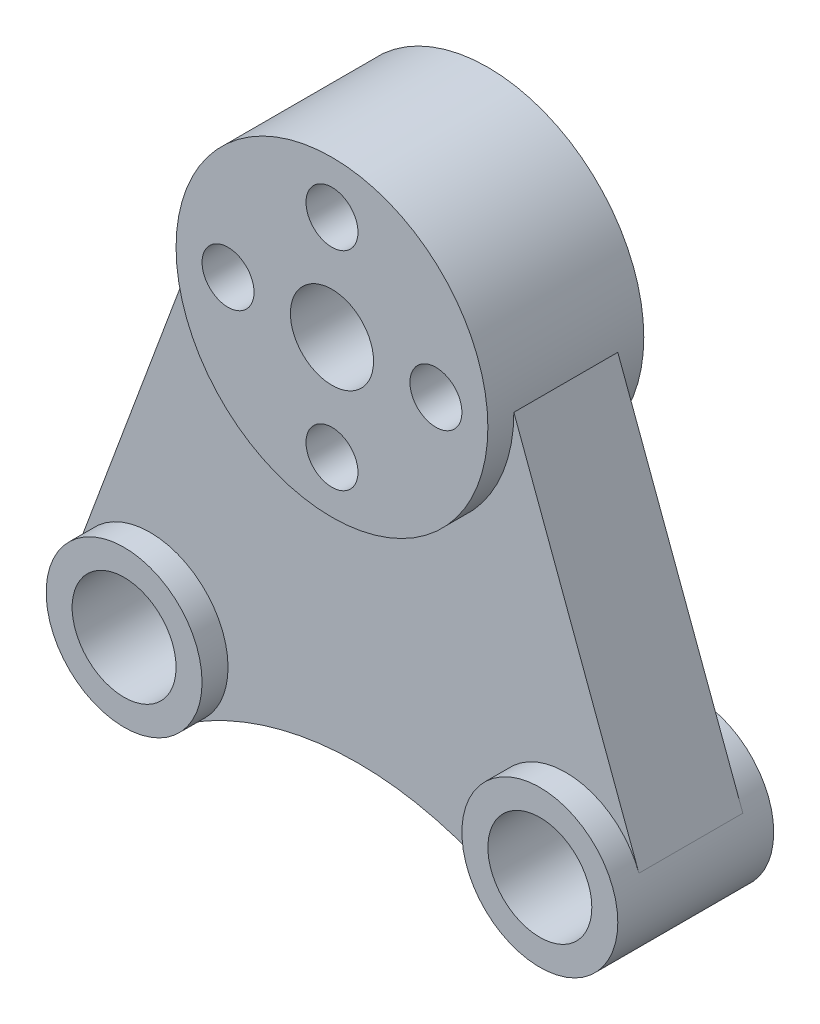
SolidWorks part; units mm, degrees
ref_plane "Front Plane" through (0, 0, 0) normal (0, 0, 1) x (1, 0, 0)
ref_plane "Top Plane" through (0, 0, 0) normal (0, 1, 0) x (1, 0, 0)
ref_plane "Right Plane" through (0, 0, 0) normal (1, 0, 0) x (0, 0, -1)
sketch "Sketch1" plane through (0, 0, 0) normal (0, 0, 1) x (1, 0, 0)
  line L0 (0, 0) -> (0, -60131.8408) construction
  line L1 (0, 0) -> (-60131.8408, 0) construction
  line L2 (-30, 0) -> (-54.0613, -64.777)
  line L3 (30, 0) -> (54.0613, -64.777)
  circle A0 centre (0, 0) radius 20 construction
  circle A1 centre (0, 0) radius 30
  circle A2 centre (0, 0) radius 8
  circle A3 centre (0, 20) radius 5
  circle A4 centre (-20, 0) radius 5
  circle A5 centre (0, -20) radius 5
  circle A6 centre (20, 0) radius 5
  circle A7 centre (40, -70) radius 15
  circle A8 centre (-40, -70) radius 15
  circle A9 centre (-40, -70) radius 10
  circle A10 centre (40, -70) radius 10
  arc A11 (-32, -82.6886) -> (32, -82.6886) centre (0, -133.4429) cw
  point P20 (0, 0)
  dimension "D1" = 40
  dimension "D2" = 60
  dimension "D3" = 16
  dimension "D4" = 10
  dimension "D6" = 30
  dimension "D7" = 30
  dimension "D9" = 20
  dimension "D10" = 20
  dimension "D13" = 60
  dimension "D8" = 70
  dimension "D11" = 40
  dimension "D12" = 40
  dimension "D5" = 4
extrude "Boss-Extrude1" add sketch "Sketch1" along normal mid plane 30 contours A8 A9 | A7 A10 | A1 A6 A5 A4 A3 A2 region at (0, 29.1515, 0) region at (-37.4217, -55.6541, 0) region at (54.3459, -67.4217, 0)
extrude "Boss-Extrude2" add sketch "Sketch1<3>" along normal mid plane 20 contours A8 A11 A7 L3 A1 L2 region at (0, -45.3527, 0)
sketch "Sketch1<3>" plane through (0, 0, 0) normal (0, 0, 1) x (1, 0, 0) same geometry as "Sketch1"
